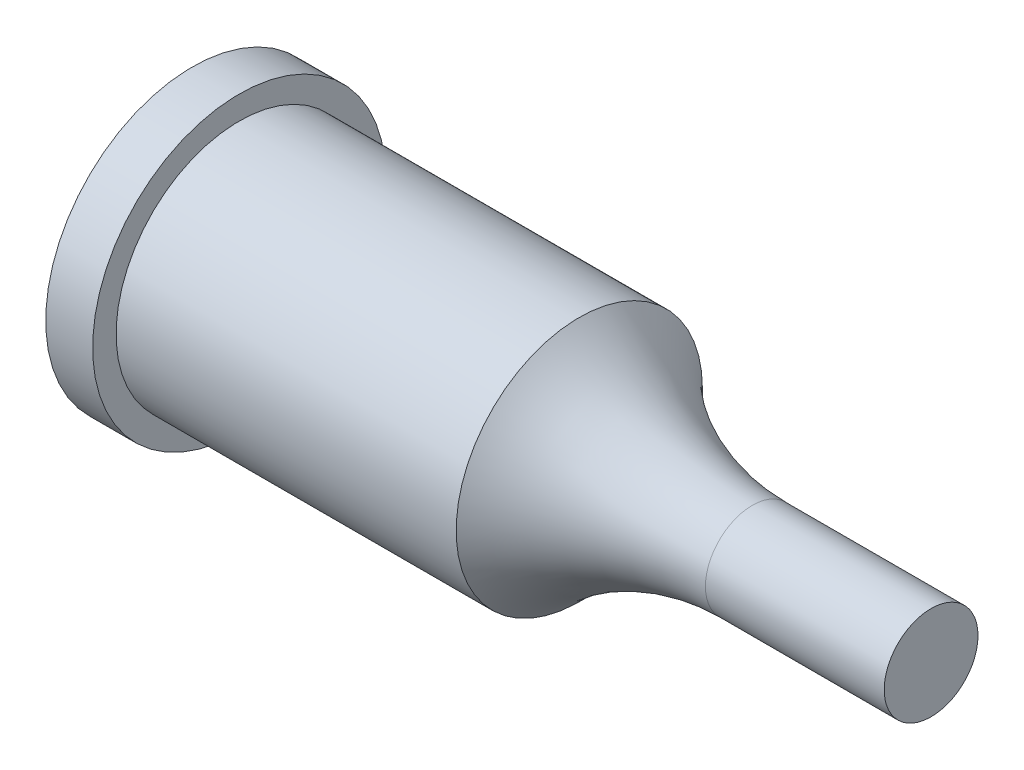
SolidWorks part; units mm, degrees
ref_plane "前视基准面" through (0, 0, 0) normal (0, 0, 1) x (1, 0, 0)
ref_plane "上视基准面" through (0, 0, 0) normal (0, 1, 0) x (1, 0, 0)
ref_plane "右视基准面" through (0, 0, 0) normal (1, 0, 0) x (0, 0, -1)
sketch "草图1" plane through (0, 0, 0) normal (0, 1, 0) x (1, 0, 0)
  line L0 (9.3412, -3.3929) -> (-49.557, -3.3929) construction
  line L1 (-20.1588, 1.8571) -> (-5.6588, 1.8571)
  line L2 (-20.1588, 1.8571) -> (-20.1588, -8.6429)
  line L3 (-20.1588, -8.6429) -> (-5.6588, -8.6429)
  line L4 (-5.6588, 1.8571) -> (-5.6588, -8.6429)
  line L5 (-22.1588, 2.8571) -> (-20.1588, 2.8571)
  line L6 (-22.1588, 2.8571) -> (-22.1588, -9.6429)
  line L7 (-22.1588, -9.6429) -> (-20.1588, -9.6429)
  line L8 (-20.1588, 2.8571) -> (-20.1588, -9.6429)
  line L9 (-5.6588, -1.3929) -> (9.3412, -1.3929)
  line L10 (-5.6588, -1.3929) -> (-5.6588, -5.3929)
  line L11 (-5.6588, -5.3929) -> (9.3412, -5.3929)
  line L12 (9.3412, -1.3929) -> (9.3412, -5.3929)
  point P8 (-22.1588, -3.3929)
  point P9 (-20.1588, -3.3929)
  point P14 (9.3412, -3.3929)
  dimension "D1" = 2
  dimension "D2" = 16.5
  dimension "D3" = 12.5
  dimension "D4" = 10.5
  dimension "D5" = 15
  dimension "D6" = 4
revolve "旋转1" add sketch "草图1" angle 360 about L0 region at (1.8412, 0, 2.3929) region at (-12.9088, 0, 0.7679) region at (-21.1588, 0, 0.2679)
fillet "圆角1" radius 10 1 edges at (-5.6588, 0, 1.3929)
